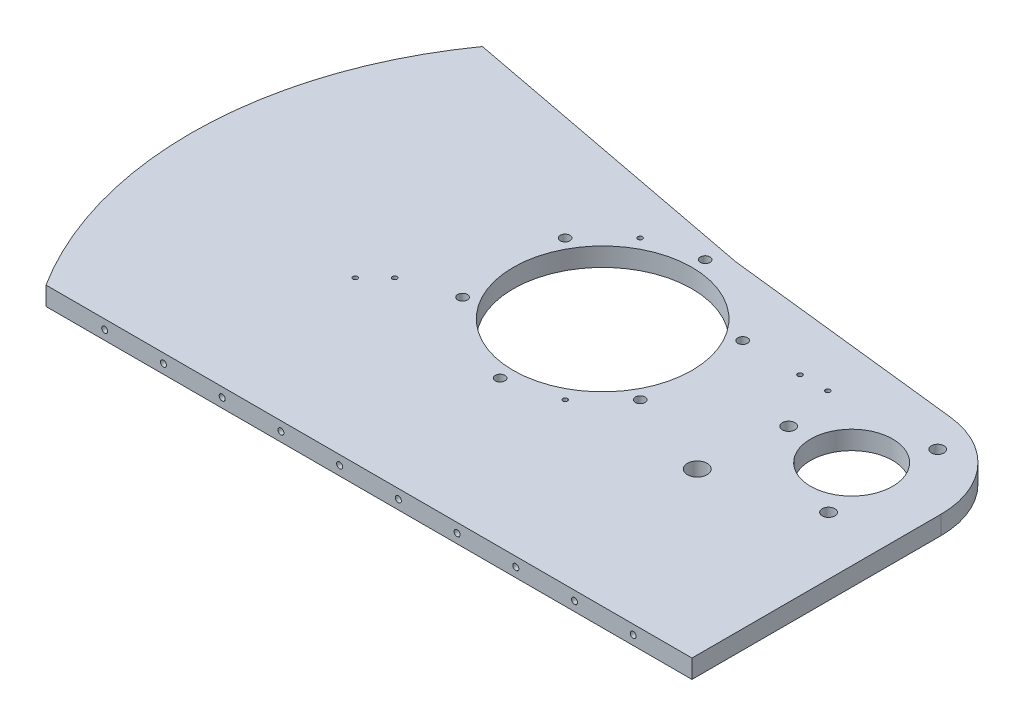
SolidWorks part; units mm, degrees
material "6061 Alloy"
ref_plane "Front Plane" through (0, 0, 0) normal (0, 0, 1) x (1, 0, 0)
ref_plane "Top Plane" through (0, 0, 0) normal (0, 1, 0) x (1, 0, 0)
ref_plane "Right Plane" through (0, 0, 0) normal (1, 0, 0) x (0, 0, -1)
sketch "Sketch1" plane through (0, 0, 0) normal (0, 1, 0) x (1, 0, 0)
  line L0 (4.4706, 39.7494) -> (88.4088, 30.3089)
  line L1 (-40, 40) -> (115.5, 40)
  line L2 (-40, 40) -> (-40, -85)
  line L3 (-40, -85) -> (115.5, -85)
  line L4 (115.5, 40) -> (115.5, -85)
  line L5 (-40, 40) -> (115.5, -85) construction
  line L6 (-40, -85) -> (115.5, 40) construction
  line L7 (-101.026, 60) -> (7.4977, 39.291)
  line L8 (-40, -85) -> (-105, -85)
  circle A0 centre (0, 0) radius 40
  circle A1 centre (0, 0) radius 30.5
  circle A2 centre (85, 0) radius 14
  circle A3 centre (85, 0) radius 30.5
  circle A5 centre (0, 0) radius 117.5 construction
  arc A6 (-101.026, 60) -> (-105, -85) centre (4.8344, -15.4558) ccw
  point P4 (37.75, -22.5)
  dimension "D3" = 80
  dimension "D4" = 61
  dimension "D5" = 61
  dimension "D6" = 28
  dimension "D2" = 235
  dimension "D8" = 130
  dimension "D1" = 85
  dimension "D7" = 85
  dimension "D9" = 65
  dimension "D10" = 20
extrude "Boss-Extrude1" add sketch "Sketch1" along normal mid plane 6.35 contours A0 L0 L1 | A0 L0 | A3 L0 A0 L2 L3 L4 | A0 A1 | A0 L1 L2 | L2 L1 | A3 A2 region at (3.6102, 0, -39.8797) region at (5.9894, 0, -39.555) region at (5.8191, 0, -38.4306) region at (41.203, 0, 46.4586) region at (-31.0653, 0, -31.0653) region at (-79.0131, 0, 14.358) region at (107.0969, 0, -19.751)
hole_wizard "M4x0.7 Tapped Hole1" positions "Sketch4" profile "Sketch5" tap size "M4x0.7" standard "ANSI Metric" end condition up to next
sketch "Sketch4" plane through (0, 3.175, 0) normal (0, 1, 0) x (1, 0, 0)
  line L0 (0, 0) -> (0, 35)
  line L1 (0, 0) -> (30.3109, 17.5)
  line L2 (0, 0) -> (30.3109, -17.5)
  line L3 (0, 0) -> (0, -35)
  line L4 (0, 0) -> (-30.3109, -17.5)
  line L5 (0, 0) -> (-30.3109, 17.5)
  point P5 (0, 35)
  point P16 (30.3109, 17.5)
  point P17 (30.3109, -17.5)
  point P18 (0, -35)
  point P19 (-30.3109, -17.5)
  point P20 (-30.3109, 17.5)
  dimension "D1" = 35
  dimension "D2" = 6
sketch "Sketch5" plane through (-30.3109, 3.175, -17.5) normal (1, 0, 0) x (0, 0, 1)
  line L0 (0, 0) -> (0, 6.35)
  line L1 (0, 6.35) -> (1.65, 6.35)
  line L2 (1.65, 6.35) -> (1.65, 0)
  line L5 (1.65, 0) -> (0, 0)
  line L11 (0, -6.35) -> (0, 107.95) construction
  dimension "Thru Tap Drill Dia." = 3.3
  dimension "Thru Tap Drill Depth" = 6.35
cosmetic thread "Hole Thread1" parameters "D2"=4
cosmetic thread "Hole Thread2" parameters "D2"=4
cosmetic thread "Hole Thread3" parameters "D2"=4
cosmetic thread "Hole Thread4" parameters "D2"=4
cosmetic thread "Hole Thread5" parameters "D2"=4
cosmetic thread "Hole Thread6" parameters "D2"=4
hole_wizard "M4 Clearance Hole1" positions "Sketch6" profile "Sketch7" hole size "M4" standard "ANSI Metric" end condition up to next
sketch "Sketch6" plane through (0, 3.175, 0) normal (0, 1, 0) x (1, 0, 0)
  line L0 (85, 0) -> (95.75, 18.6195)
  line L1 (85, 0) -> (95.75, -18.6195)
  line L2 (85, 0) -> (63.5, 0)
  point P2 (95.75, 18.6195)
  point P10 (95.75, -18.6195)
  point P11 (63.5, 0)
  dimension "D1" = 21.5
  dimension "D2" = 3
sketch "Sketch7" plane through (63.5, 3.175, 0) normal (1, 0, 0) x (0, 0, 1)
  line L0 (0, 0) -> (0, 6.35)
  line L1 (0, 6.35) -> (2.15, 6.35)
  line L2 (2.15, 6.35) -> (2.15, 0)
  line L5 (2.15, 0) -> (0, 0)
  line L11 (0, -6.35) -> (0, 107.95) construction
  dimension "Thru Hole Dia." = 4.3
  dimension "Thru Hole Depth" = 6.35
hole_wizard "M2.5x0.45 Tapped Hole1" positions "Sketch8" profile "Sketch9" tap size "M2.5x0.45" standard "ANSI Metric"
sketch "Sketch8" plane through (0, 0, 85) normal (0, 0, 1) x (1, 0, 0)
  line L0 (-105, 0) -> (-84.9545, 0) construction
  line L1 (-105, 3.175) -> (-105, -3.175) construction
  line L2 (-84.9545, 0) -> (-64.9091, 0) construction
  line L3 (-64.9091, 0) -> (-44.8636, 0) construction
  line L4 (-44.8636, 0) -> (-24.8182, 0) construction
  line L5 (-24.8182, 0) -> (-4.7727, 0) construction
  line L6 (-4.7727, 0) -> (15.2727, 0) construction
  line L7 (15.2727, 0) -> (35.3182, 0) construction
  line L8 (35.3182, 0) -> (55.3636, 0) construction
  line L9 (55.3636, 0) -> (75.4091, 0) construction
  line L10 (75.4091, 0) -> (95.4545, 0) construction
  line L11 (95.4545, 0) -> (115.5, 0) construction
  line L12 (115.5, 3.175) -> (115.5, -3.175) construction
  point P4 (-84.9545, 0)
  point P9 (-64.9091, 0)
  point P11 (-44.8636, 0)
  point P13 (-24.8182, 0)
  point P15 (-4.7727, 0)
  point P17 (15.2727, 0)
  point P19 (35.3182, 0)
  point P21 (55.3636, 0)
  point P23 (75.4091, 0)
  point P25 (95.4545, 0)
sketch "Sketch9" plane through (95.4545, 0, 85) normal (1, 0, 0) x (0, -1, 0)
  line L0 (0, 0) -> (0, 15.6159)
  line L1 (0, 15.6159) -> (1.025, 15)
  line L2 (1.025, 15) -> (1.025, 0)
  line L5 (1.025, 0) -> (0, 0)
  line L10 (0, 15.6159) -> (-1.025, 15) construction
  line L11 (0, -6.35) -> (0, 107.95) construction
  dimension "Tap Drill Dia." = 2.05
  dimension "Tap Drill Depth" = 15
  dimension "Drill Angle" = 118
cosmetic thread "Hole Thread7" parameters "D1"=5, "D2"=2.5
cosmetic thread "Hole Thread8" parameters "D1"=5, "D2"=2.5
cosmetic thread "Hole Thread9" parameters "D1"=5, "D2"=2.5
cosmetic thread "Hole Thread10" parameters "D1"=5, "D2"=2.5
cosmetic thread "Hole Thread11" parameters "D1"=5, "D2"=2.5
cosmetic thread "Hole Thread12" parameters "D1"=5, "D2"=2.5
cosmetic thread "Hole Thread13" parameters "D1"=5, "D2"=2.5
cosmetic thread "Hole Thread14" parameters "D1"=5, "D2"=2.5
cosmetic thread "Hole Thread15" parameters "D1"=5, "D2"=2.5
cosmetic thread "Hole Thread16" parameters "D1"=5, "D2"=2.5
hole_wizard "M2.5x0.45 Tapped Hole2" positions "3DSketch1" profile "Sketch10" tap size "M2.5x0.45" standard "ANSI Metric"
sketch3d "3DSketch1"
  line L0 (-105, 3.175, 85) -> (-105, -3.175, 85) construction
  line L1 (-107.593, -3.175, 80.7249) -> (-107.593, 0, 80.7249)
  arc A0 (-101.026, -3.175, -60) -> (-105, -3.175, 85) centre (4.8344, -3.175, 15.4558) ccw construction
  point P0 (-107.593, 0, 80.7249)
  point P10 (4.8344, 126.825, 15.4558)
  dimension "D1" = 5
  dimension "D2" = 3.175
sketch "Sketch10" plane through (-107.593, 0, 80.7249) normal (0, 1, 0) x (0.5021, 0, 0.8648)
  line L0 (0, 0) -> (0, 15.6159)
  line L1 (0, 15.6159) -> (1.025, 15)
  line L2 (1.025, 15) -> (1.025, 0)
  line L5 (1.025, 0) -> (0, 0)
  line L10 (0, 15.6159) -> (-1.025, 15) construction
  line L11 (0, -6.35) -> (0, 107.95) construction
  dimension "Tap Drill Dia." = 2.05
  dimension "Tap Drill Depth" = 15
  dimension "Drill Angle" = 118
cosmetic thread "Hole Thread17" parameters "D1"=5, "D2"=2.5
pattern_circular "CirPattern1" count 4 over 62.5 about axis through (4.8344, 3.175, 15.4558) along (0, -1, 0) of "M2.5x0.45 Tapped Hole2"
cosmetic thread "Hole Thread18" parameters "D1"=5, "D2"=2.5
cosmetic thread "Hole Thread19" parameters "D1"=5, "D2"=2.5
cosmetic thread "Hole Thread20" parameters "D1"=5, "D2"=2.5
hole_wizard "1/4 Clearance Hole1" positions "Sketch11" profile "Sketch12" hole size "1/4" standard "ANSI Inch" end condition up to next
sketch "Sketch11" plane through (0, 3.175, 0) normal (0, 1, 0) x (1, 0, 0)
  line L0 (60.5414, -28.2309) -> (0, 0)
  line L1 (0, 0) -> (30.5, 0)
  circle A1 centre (60.5414, -28.2309) radius 3.175
  circle A2 centre (0, 0) radius 30.5 construction
  point P0 (60.5414, -28.2309)
  dimension "D1" = 6.35
  dimension "D2" = 66.8
  dimension "D3" = 25
sketch "Sketch12" plane through (60.5414, 3.175, 28.2309) normal (1, 0, 0) x (0, 0, 1)
  line L0 (0, 0) -> (0, 6.35)
  line L1 (0, 6.35) -> (3.3782, 6.35)
  line L2 (3.3782, 6.35) -> (3.3782, 0)
  line L5 (3.3782, 0) -> (0, 0)
  line L11 (0, -6.35) -> (0, 107.95) construction
  dimension "Thru Hole Dia." = 6.7564
  dimension "Thru Hole Depth" = 6.35
hole_wizard "M2x0.4 Tapped Hole1" positions "Sketch13" profile "Sketch14" tap size "M2x0.4" standard "ANSI Metric" end condition up to next
sketch "Sketch13" plane through (0, 3.175, 0) normal (0, 1, 0) x (1, 0, 0)
  line L0 (-54.3468, -30.0803) -> (-47.6293, -23.3628)
  line L2 (0, 0) -> (-50.2046, -50.2046)
  line L4 (0, 0) -> (71, 0)
  line L6 (0, 0) -> (-21.5668, 21.5668)
  line L8 (-17.5, 30.3109) -> (17.5, -30.3109)
  line L9 (50.2, 17.159) -> (59.7, 17.159)
  line L11 (0, 0) -> (0, 30.5)
  circle A0 centre (0, 0) radius 30.5 construction
  circle A1 centre (85, 0) radius 14 construction
  point P0 (-47.6293, -23.3628)
  point P2 (-54.3468, -30.0803)
  point P87 (0, 0)
  point P92 (-17.5, 30.3109)
  point P95 (17.5, -30.3109)
  point P113 (50.2, 17.159)
  point P116 (59.7, 17.159)
  dimension "D1" = 9.5
  dimension "D2" = 135
  dimension "D3" = 17.159
  dimension "D4" = 50.199
  dimension "D5" = 70
  dimension "D6" = 120
  dimension "D7" = 9.5
  dimension "D8" = 17.159
  dimension "D9" = 50.2
sketch "Sketch14" plane through (-47.6293, 3.175, 23.3628) normal (1, 0, 0) x (0, 0, 1)
  line L0 (0, 0) -> (0, 6.35)
  line L1 (0, 6.35) -> (0.8, 6.35)
  line L2 (0.8, 6.35) -> (0.8, 0)
  line L5 (0.8, 0) -> (0, 0)
  line L11 (0, -6.35) -> (0, 107.95) construction
  dimension "Thru Tap Drill Dia." = 1.6
  dimension "Thru Tap Drill Depth" = 6.35
cosmetic thread "Hole Thread21" parameters "D2"=2
cosmetic thread "Hole Thread22" parameters "D2"=2
cosmetic thread "Hole Thread23" parameters "D2"=2
cosmetic thread "Hole Thread24" parameters "D2"=2
cosmetic thread "Hole Thread25" parameters "D2"=2
cosmetic thread "Hole Thread26" parameters "D2"=2
